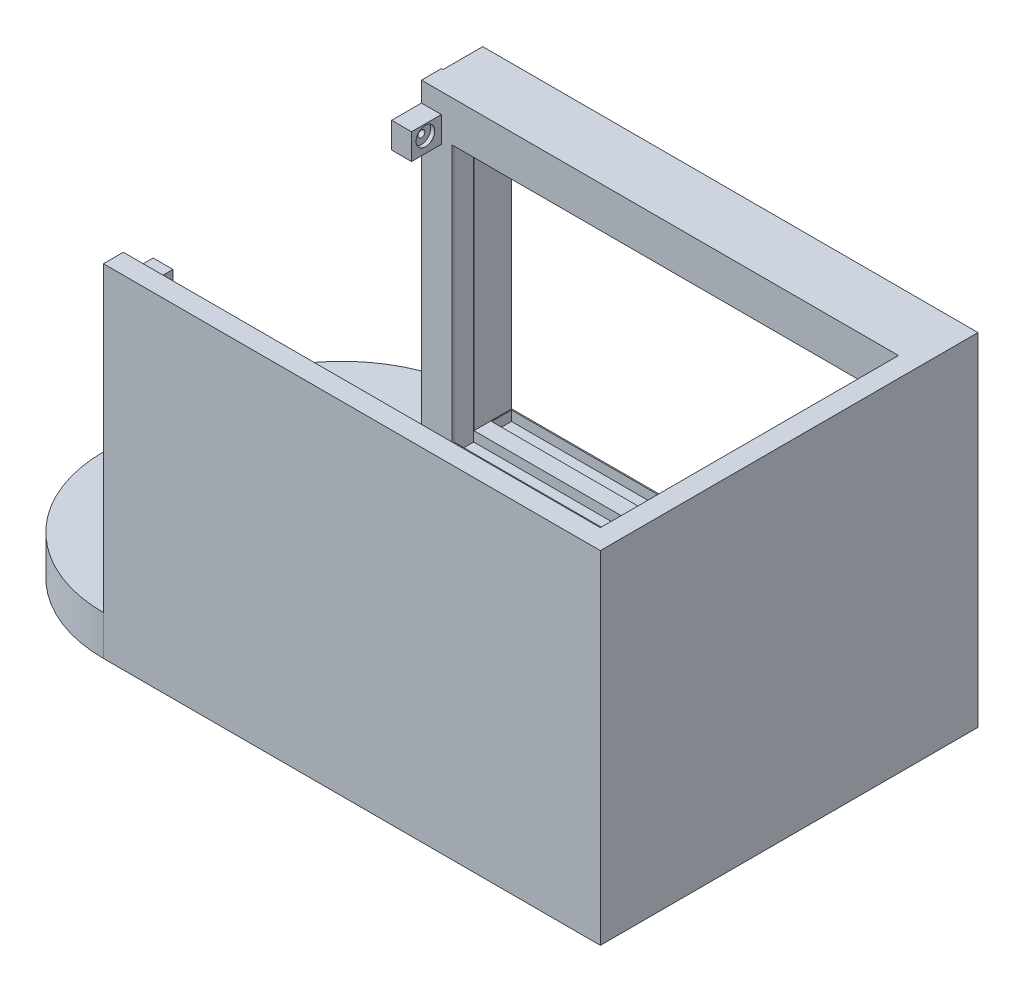
SolidWorks part; units mm, degrees
ref_plane "Front Plane" through (0, 0, 0) normal (0, 0, 1) x (1, 0, 0)
ref_plane "Top Plane" through (0, 0, 0) normal (0, 1, 0) x (1, 0, 0)
ref_plane "Right Plane" through (0, 0, 0) normal (1, 0, 0) x (0, 0, -1)
sketch "Sketch1" plane through (0, 0, 0) normal (0, 1, 0) x (1, 0, 0)
  line L1 (-125, -85) -> (125, -85)
  line L2 (-125, -85) -> (-125, 85)
  line L3 (-125, 85) -> (125, 85)
  line L4 (125, -85) -> (125, 85)
  line L5 (-125, 85) -> (-125, 105)
  line L6 (-125, 105) -> (-195, 105)
  line L7 (-195, 85) -> (-195, -85)
  line L8 (-195, -85) -> (-125, -85)
  line L9 (-125, 75) -> (115, 75)
  line L10 (115, -75) -> (115, 75)
  line L11 (-125, -75) -> (115, -75)
  line L14 (-195, 105) -> (-195, 85)
  point P0 (0, 0)
  dimension "D1" = 170
  dimension "D2" = 250
  dimension "D3" = 70
  dimension "D4" = 10
  dimension "D5" = 20
extrude "Boss-Extrude1" add sketch "Sketch1" along normal blind 172 contours L11 L2 L1 L4 L3 L9 L10 region at (-121.9768, 0, 80)
extrude "Boss-Extrude2" add sketch "Sketch1<3>" along normal blind 20 contours L7 L8 L2 | L2 L11 L10 L9 region at (-160, 0, -10) region at (-5, 0, 0)
sketch "Sketch1<3>" plane through (0, 0, 0) normal (0, 1, 0) x (1, 0, 0) same geometry as "Sketch1"
sketch "Sketch2" plane through (0, 0, -75) normal (0, 0, 1) x (1, 0, 0)
  line L0 (-125, 172) -> (125, 172) construction
  line L1 (-125, 149) -> (-115, 149)
  line L2 (-125, 149) -> (-125, 162)
  line L3 (-125, 162) -> (-115, 162)
  line L4 (-115, 149) -> (-115, 162)
  line L5 (-125, 172) -> (-125, 20) construction
  dimension "D1" = 13
  dimension "D2" = 10
  dimension "D3" = 10
  dimension "D4" = 0
extrude "Boss-Extrude3" add sketch "Sketch2" along normal blind 15
hole_wizard "CBORE for M3 Hex Head Cap Screw1" positions "Sketch4" profile "Sketch5" counterbore size "M3" standard "ISO" end condition through all
sketch "Sketch4" plane through (-115, 0, 0) normal (1, 0, 0) x (0, 0, -1)
  line L0 (60, 149) -> (60, 162) construction
  point P0 (67, 156.6121)
  dimension "D1" = 7
sketch "Sketch5" plane through (-115, 156.6121, -67) normal (0, 1, 0) x (0, 0, -1)
  line L0 (0, 0) -> (0, 80)
  line L1 (0, 80) -> (1.7, 80)
  line L3 (1.7, 80) -> (1.7, 2)
  line L4 (4.6755, 2) -> (1.7, 2)
  line L5 (4.6755, 2) -> (4.6755, 0.025)
  line L6 (4.6755, 0.025) -> (4.7005, 0)
  line L7 (4.7005, 0) -> (0, 0)
  line L8 (-4.6755, 0.025) -> (-4.7005, 0) construction
  line L11 (0, -6.35) -> (0, 107.95) construction
  dimension "Thru Hole Dia." = 3.4
  dimension "Thru Hole Depth" = 80
  dimension "C'Bore Dia." = 9.351
  dimension "C'Bore Depth" = 2
  dimension "Near C'Sink Dia." = 9.401
  dimension "Near C'Sink Angle" = 90
ref_plane "Plane1" through (0, 0, 0) normal (0, 0, 1) x (1, 0, 0)
mirror "Mirror1" about plane through (0, 0, 0) normal (0, 0, 1) of "CBORE for M3 Hex Head Cap Screw1", "Boss-Extrude3"
sketch "Sketch6" plane through (0, 0, 75) normal (0, 0, -1) x (-1, 0, 0)
  line L1 (114.3776, 19.8322) -> (107.3776, 19.8322)
  line L2 (114.3776, 19.8322) -> (114.3776, 102.8078)
  line L3 (114.3776, 102.8078) -> (107.3776, 102.8078)
  line L4 (107.3776, 19.8322) -> (107.3776, 102.8078)
  line L5 (67.3776, 19.7039) -> (60.3776, 19.7039)
  line L6 (67.3776, 19.7039) -> (67.3776, 102.6796)
  line L7 (67.3776, 102.6796) -> (60.3776, 102.6796)
  line L8 (60.3776, 19.7039) -> (60.3776, 102.6796)
  dimension "D1" = 40
  dimension "D2" = 7
extrude "Boss-Extrude4" add sketch "Sketch6" along normal blind 15
sketch "Sketch9" plane through (0, 0, -85) normal (0, 0, -1) x (-1, 0, 0)
  line L0 (-125, 172) -> (-125, 0) construction
  line L1 (-125, 172) -> (124.1723, 172)
  line L2 (-125, 172) -> (-125, 0)
  line L3 (-125, 0) -> (124.1723, 0)
  line L4 (124.1723, 172) -> (124.1723, 0)
  line L5 (125, 172) -> (-125, 172) construction
  line L6 (125, 0) -> (-125, 0) construction
extrude "Boss-Extrude7" add sketch "Sketch9" along normal blind 20
sketch "Sketch11" plane through (0, 0, -105) normal (0, 0, -1) x (-1, 0, 0)
  line L0 (-0.4138, 172) -> (-0.4138, 0.9682) construction
  line L1 (124.1723, 172) -> (-125, 172) construction
  line L2 (-125, 86) -> (125, 86) construction
  line L3 (-125, 172) -> (-125, 0) construction
  line L4 (125, 172) -> (125, 20) construction
  line L6 (-110.4138, 21.4841) -> (109.5862, 21.4841)
  line L7 (-110.4138, 21.4841) -> (-110.4138, 151.4841)
  line L8 (-110.4138, 151.4841) -> (109.5862, 151.4841)
  line L9 (109.5862, 21.4841) -> (109.5862, 151.4841)
  line L10 (-110.4138, 21.4841) -> (109.5862, 151.4841) construction
  line L11 (-110.4138, 151.4841) -> (109.5862, 21.4841) construction
  point P10 (-0.4138, 86.4841)
  dimension "D1" = 220
  dimension "D2" = 130
extrude "Cut-Extrude3" cut sketch "Sketch11" against normal blind 75 and the other way blind 75
sketch "Sketch12" plane through (0, 21.4841, 0) normal (0, 1, 0) x (1, 0, 0)
  line L1 (-109.1363, 104.4161) -> (110.8637, 104.4161)
  line L2 (-109.1363, 104.4161) -> (-109.1363, 94.4161)
  line L3 (-109.1363, 94.4161) -> (110.8637, 94.4161)
  line L4 (110.8637, 104.4161) -> (110.8637, 94.4161)
  line L5 (-109.6928, 75.9814) -> (110.3072, 75.9814)
  line L6 (-109.6928, 75.9814) -> (-109.6928, 85.9814)
  line L7 (-109.6928, 85.9814) -> (110.3072, 85.9814)
  line L8 (110.3072, 75.9814) -> (110.3072, 85.9814)
  dimension "D1" = 220
  dimension "D2" = 10
  dimension "D3" = 10
  dimension "D4" = 220
extrude "Cut-Extrude4" cut sketch "Sketch12" against normal blind 5 and the other way blind 135
fillet "Fillet2" radius 70 2 edges at (-195, 10, 85) (-195, 10, -105)
